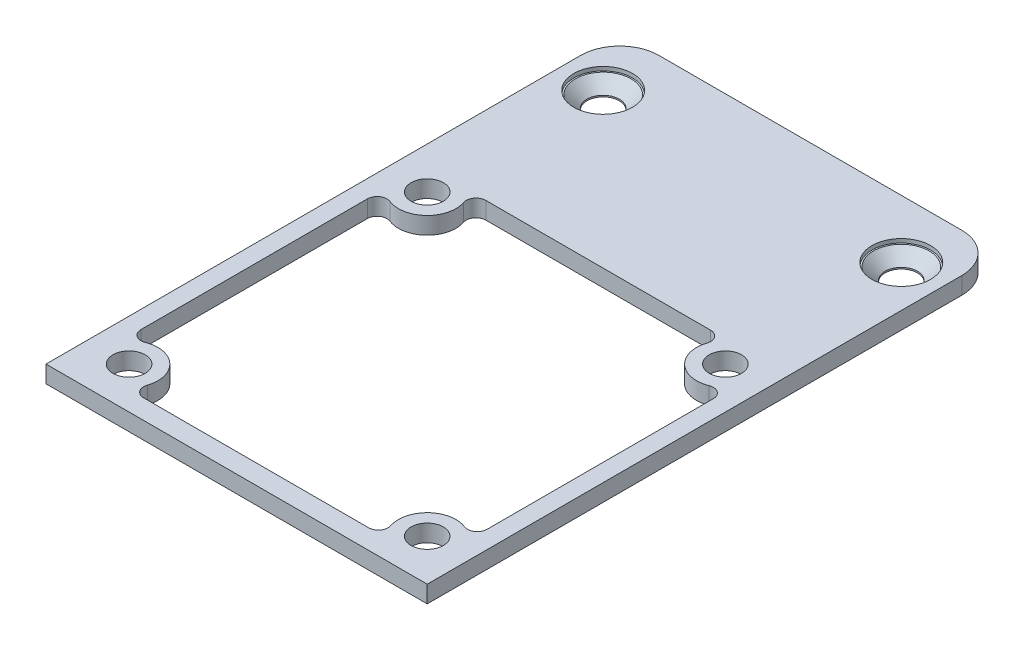
SolidWorks part; units mm, degrees
ref_plane "Front Plane" through (0, 0, 0) normal (0, 0, 1) x (1, 0, 0)
ref_plane "Top Plane" through (0, 0, 0) normal (0, 1, 0) x (1, 0, 0)
ref_plane "Right Plane" through (0, 0, 0) normal (1, 0, 0) x (0, 0, -1)
sketch "Sketch1" plane through (0, 0, 0) normal (0, 1, 0) x (1, 0, 0)
  line L0 (-15.5, 39.2) -> (15.5, 39.2)
  line L1 (-18.2, 15) -> (-18.2, -15) construction
  line L2 (17.7, -17.4996) -> (-17.7, -17.4996)
  line L3 (17.7, -17.4996) -> (17.7, 17.4996)
  line L4 (17.7, 17.4996) -> (-17.7, 17.4996)
  line L5 (-17.7, -17.4996) -> (-17.7, 17.4996)
  line L6 (17.7, -17.4996) -> (-17.7, 17.4996) construction
  line L7 (-19.5, 35.2) -> (-19.5, -19.5)
  line L8 (-19.5, -19.5) -> (19.5, -19.5)
  line L9 (19.5, -19.5) -> (19.5, 35.2)
  line L10 (17.7, 17.4996) -> (-17.7, -17.4996) construction
  line L11 (-15.25, 15.25) -> (-15.25, 17.9996) construction
  arc A0 (19.5, 35.2) -> (15.5, 39.2) centre (15.5, 35.2) ccw construction
  arc A1 (-15.5, 39.2) -> (-19.5, 35.2) centre (-15.5, 35.2) ccw construction
  arc A2 (19.5, 35.2) -> (15.5, 39.2) centre (15.5, 35.2) ccw
  arc A3 (-15.5, 39.2) -> (-19.5, 35.2) centre (-15.5, 35.2) ccw
  circle A4 centre (-15.25, -15.25) radius 1.65 construction
  circle A5 centre (15.25, -15.25) radius 1.65 construction
  circle A6 centre (-15.25, 15.25) radius 1.65 construction
  circle A7 centre (15.25, 15.25) radius 1.65 construction
  circle A8 centre (-15.25, 33.25) radius 1.65 construction
  circle A9 centre (15.25, 33.25) radius 1.65 construction
  circle A10 centre (-15.25, -15.25) radius 1.65
  circle A11 centre (15.25, -15.25) radius 1.65
  circle A12 centre (-15.25, 15.25) radius 1.65
  circle A13 centre (15.25, 15.25) radius 1.65
  circle A14 centre (-15.25, 33.25) radius 1.65
  circle A15 centre (15.25, 33.25) radius 1.65
  arc A16 (-15.2, 18) -> (-18.2, 15) centre (-15.2, 15) ccw construction
  circle A17 centre (-15.25, 15.25) radius 2.95
  circle A18 centre (15.25, 15.25) radius 2.95
  circle A19 centre (-15.25, -15.25) radius 2.95
  circle A20 centre (15.25, -15.25) radius 2.95
  point P29 (0, 0)
  dimension "D1" = 0.5
  dimension "D2" = 0.5
extrude "Base shape" add sketch "Sketch1" along normal blind 1.75 contours L0 A3 L7 L8 L9 A2 A20 L3 L2 A19 L5 A17 L4 A18 A15 A14 | A17 L4 L5 | L4 A17 L5 A12 | L5 A17 | L4 A17 | L3 A18 L4 A13 | L3 A18 | L4 A18 | L2 A19 L5 A10 | L2 A19 | L5 A19 | A19 L5 L2 | L2 A20 L3 A11 | L3 A20 | L2 A20 | A20 L2 L3 | A18 L3 L4 region at (0, 0, -21.4057) region at (17.5279, 0, 17.307) region at (15.25, 0, 17.7828) region at (15.25, 0, 17.4246) region at (17.9015, 0, 15.25) region at (-15.25, 0, 17.7828) region at (-15.25, 0, 17.4246) region at (13.3348, 0, -13.1057) region at (17.9015, 0, -15.25) region at (-17.5279, 0, 17.307) region at (17.5279, 0, -17.307) region at (15.25, 0, -17.7828) region at (-17.9015, 0, 15.25) region at (-12.6411, 0, -16.458) region at (-15.25, 0, -17.7828) region at (-17.9015, 0, -15.25) region at (-17.5279, 0, -17.307)
fillet "Milling fillets" radius 1 8 edges at (-17.7, 0.875, 13.6068) (-13.3416, 0.875, 17.4996) (13.3416, 0.875, 17.4996) (17.7, 0.875, 13.6068) (17.7, 0.875, -13.6068) (13.3416, 0.875, -17.4996) (-13.3416, 0.875, -17.4996) (-17.7, 0.875, -13.6068)
sketch "Sketch3" plane through (0, 1.75, 0) normal (0, 1, 0) x (1, 0, 0)
  circle A0 centre (-15.25, 33.25) radius 3
  circle A1 centre (15.25, 33.25) radius 3
  dimension "D1" = 6
extrude "Screw head cut" cut sketch "Sketch3" against normal blind 0.4
chamfer "Screw head chamfer" distance 1.2 angle 45 2 edges at (15.25, 1.35, -31.6) (-15.25, 1.35, -31.6)
